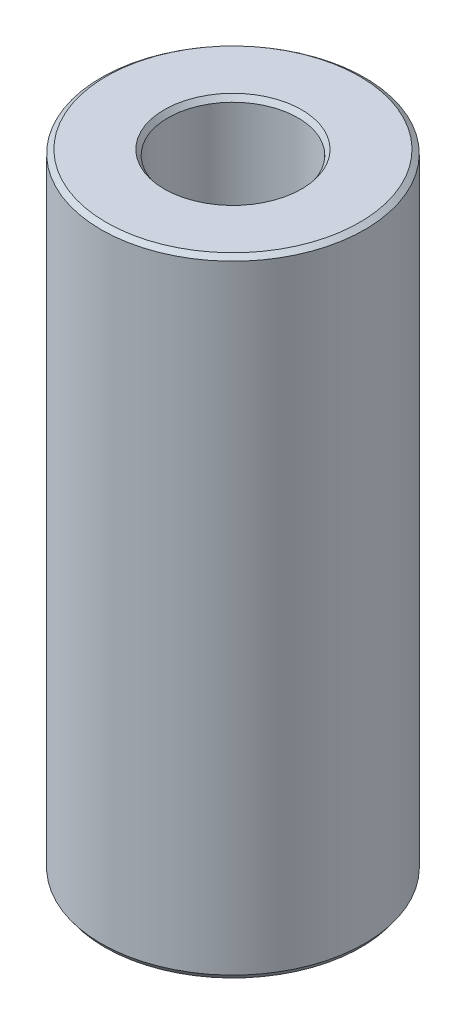
SolidWorks part; units mm, degrees
ref_plane "Front Plane" through (0, 0, 0) normal (0, 0, 1) x (1, 0, 0)
ref_plane "Top Plane" through (0, 0, 0) normal (0, 1, 0) x (1, 0, 0)
ref_plane "Right Plane" through (0, 0, 0) normal (1, 0, 0) x (0, 0, -1)
sketch "Sketch1" plane through (0, 0, 0) normal (0, 1, 0) x (1, 0, 0)
  circle A0 centre (0, 0) radius 37.5
  dimension "SLEEVE_OD" = 75
extrude "Boss-Extrude1" add sketch "Sketch1" along normal blind 178.4898
sketch "Sketch2" plane through (0, 0, 0) normal (0, 1, 0) x (1, 0, 0)
  circle A0 centre (0, 0) radius 18.4957
  dimension "BORE_D" = 36.9914
extrude "Cut-Extrude1" cut sketch "Sketch2" along normal through all
chamfer "Chamfer1" distance 1.0588 angle 54.033 4 edges at (0, 178.4898, 18.4957) (0, 0, 18.4957) (0, 0, 37.5) (0, 178.4898, 37.5) first distance on face at (0, 178.4898, 18.4957) first distance on face at (0, 0, 18.4957) first distance on face at (0, 178.4898, 37.5)
